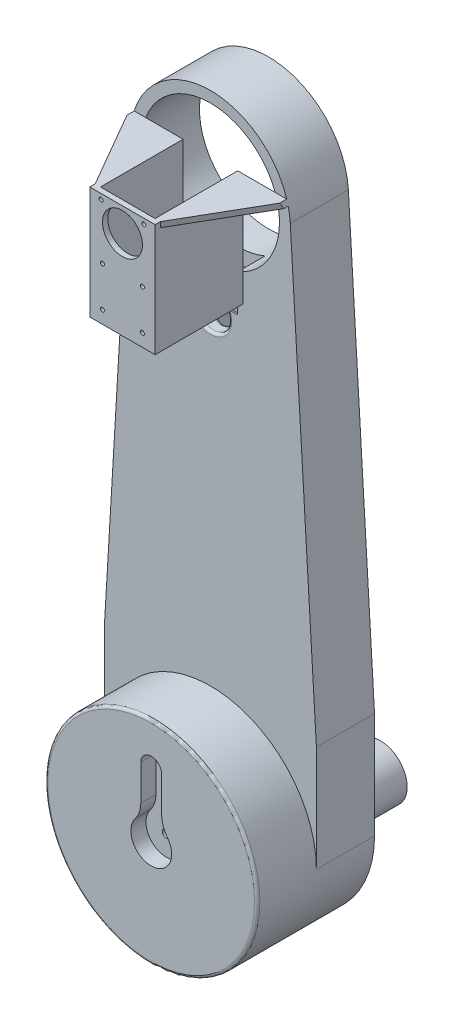
SolidWorks part; units mm, degrees
material "6061 Alloy"
ref_plane "Front Plane" through (0, 0, 0) normal (0, 0, 1) x (1, 0, 0)
ref_plane "Top Plane" through (0, 0, 0) normal (0, 1, 0) x (1, 0, 0)
ref_plane "Right Plane" through (0, 0, 0) normal (1, 0, 0) x (0, 0, -1)
sketch "Sketch1" plane through (0, 0, 0) normal (0, 0, 1) x (1, 0, 0)
  circle A0 centre (0, 0) radius 39.75
  dimension "D1" = 79.5
extrude "Boss-Extrude1" add sketch "Sketch1" along normal blind 44
sketch "Sketch2" plane through (0, 0, 0) normal (0, 1, 0) x (1, 0, 0)
  line L0 (39.75, -44) -> (39.75, 0) construction
  line L1 (-39.75, 0) -> (39.75, 0)
  line L2 (-39.75, 0) -> (-39.75, -21.8)
  line L3 (-39.75, -21.8) -> (39.75, -21.8)
  line L4 (39.75, 0) -> (39.75, -21.8)
  dimension "D1" = 21.8
extrude "Boss-Extrude2" add sketch "Sketch2" along normal through all
sketch "Sketch3" plane through (0, 0, 0) normal (0, 0, -1) x (-1, 0, 0)
  line L0 (0, 0) -> (0, 203.2) construction
  line L1 (-39.75, 39.75) -> (-29.9473, 204.9767)
  line L2 (39.75, 39.75) -> (29.9473, 204.9767)
  line L3 (39.75, 39.75) -> (39.75, 0) construction
  line L4 (-39.75, 39.75) -> (39.75, 39.75) construction
  circle A0 centre (0, 203.2) radius 30
  line M5 (39.75, 39.75) -> (-39.75, 39.75)
  dimension "D1" = 60
  dimension "D2" = 203.2
extrude "Boss-Extrude3" add sketch "Sketch3" against normal up to surface (21.8 mm away) contours L0 A0 L1 M5 | L0 L2 A0 M5 | A0 region at (18.2462, 107.3979, 0) region at (-18.2462, 107.3979, 0) region at (21.2148, 183.2065, 0) up to face at (29.2442, 29.2442, 21.8)
ref_plane "Plane7" through (0, 233.2, 0) normal (0, 1, 0) x (1, 0, 0)
sketch "Sketch5" plane through (0, 0, 21.8) normal (0, 0, 1) x (1, 0, 0)
  line L0 (10.25, 179.4146) -> (10.25, 171.95)
  line L1 (10.25, 171.95) -> (-10.25, 171.95)
  line L2 (-10.25, 171.95) -> (-10.25, 179.4146)
  circle A0 centre (0, 203.2) radius 25.9
  dimension "D1" = 20.5
  dimension "D4" = 51.8
  dimension "D6" = 7.4646
  dimension "D7" = 7.4646
extrude "Cut-Extrude2" cut sketch "Sketch5" against normal up to next contours A0 region at (0, 203.2, 21.8)
extrude "Cut-Extrude3" cut sketch "Sketch5<3>" against normal blind 10.25 contours A0 L2 L1 L0 region at (0, 175.0039, 21.8)
sketch "Sketch5<3>" plane through (0, 0, 21.8) normal (0, 0, 1) x (1, 0, 0) same geometry as "Sketch5"
sketch "Sketch7" plane through (0, 0, 21.8) normal (0, 0, 1) x (1, 0, 0)
  line L0 (-10.25, 171.95) -> (-10.25, 179.4146) construction
  line L1 (10.25, 171.95) -> (-12.25, 171.95)
  line L2 (10.25, 171.95) -> (10.25, 169.95)
  line L3 (10.25, 169.95) -> (-12.25, 169.95)
  line L4 (-12.25, 171.95) -> (-12.25, 169.95)
  line L6 (10.25, 169.95) -> (12.25, 169.95)
  line L7 (10.25, 169.95) -> (10.25, 212.2)
  line L8 (10.25, 212.2) -> (12.25, 212.2)
  line L9 (12.25, 169.95) -> (12.25, 212.2)
  line L10 (-12.25, 212.2) -> (-28.6182, 212.2)
  line L11 (-10.25, 171.95) -> (-12.25, 171.95)
  line L12 (-10.25, 171.95) -> (-10.25, 212.2)
  line L13 (-10.25, 212.2) -> (-12.25, 212.2)
  line L14 (-12.25, 171.95) -> (-12.25, 212.2)
  line L15 (-12.25, 210.2) -> (-29.1719, 210.2)
  line L16 (12.25, 212.2) -> (28.6182, 212.2)
  line L17 (12.25, 210.2) -> (29.1719, 210.2)
  line L18 (0, 203.2) -> (0, 212.2) construction
  line L19 (-10.25, 212.2) -> (10.25, 212.2) construction
  arc A0 (29.9473, 204.9767) -> (-29.9473, 204.9767) centre (0, 203.2) ccw construction
  arc A1 (-28.6182, 212.2) -> (-29.1719, 210.2) centre (0, 203.2) ccw
  arc A2 (29.1719, 210.2) -> (28.6182, 212.2) centre (0, 203.2) ccw
  arc M13 (29.9473, 204.9767) -> (-29.9473, 204.9767) centre (0, 203.2) ccw
  line M15 (10.25, 179.4146) -> (10.25, 171.95)
  line M16 (10.25, 171.95) -> (-10.25, 171.95)
  line M17 (-10.25, 171.95) -> (-10.25, 179.4146)
  arc M18 (-10.25, 179.4146) -> (10.25, 179.4146) centre (0, 203.2) cw
  dimension "D9" = 30
  dimension "D1" = 2
  dimension "D2" = 2
  dimension "D3" = 2
  dimension "D4" = 2
  dimension "D5" = 2
  dimension "D6" = 2
  dimension "D7" = 9
  dimension "D8" = 42.25
extrude "Boss-Extrude5" add sketch "Sketch7" along normal blind 31 contours L15 L14 L10 M18 | L15 L10 M18 M13 | L14 L12 L13 M18 | L14 L1 M17 M18 | L1 L4 L3 L2 M16 | L6 L9 L2 M18 M15 | L9 L8 L7 M18 | L9 L17 L16 M18 | L17 L16 M18 M13 region at (-1, 170.95, 21.8) region at (11.2662, 174.9188, 21.8) region at (-11.2703, 175.9197, 21.8) region at (11.245, 196.0386, 21.8) region at (-11.245, 196.0386, 21.8) region at (18.4394, 211.1912, 21.8) region at (26.7656, 211.2037, 21.8) region at (-18.4394, 211.1912, 21.8) region at (-26.7656, 211.2037, 21.8)
sketch "Sketch8" plane through (0, 212.2, 0) normal (0, 1, 0) x (1, 0, 0)
  line L0 (-29.1719, -23.4904) -> (-12.25, -52.8)
  line L1 (29.1719, -52.8) -> (29.1719, -21.8) construction
  line L2 (12.25, -52.8) -> (29.1719, -23.4904)
  line L4 (-29.1719, -52.8) -> (-29.1719, -21.8) construction
  line L6 (-29.1719, -23.4904) -> (-29.1719, -52.8)
  line L7 (-29.1719, -52.8) -> (-12.25, -52.8)
  line L8 (12.25, -52.8) -> (29.1719, -52.8)
  line L9 (29.1719, -52.8) -> (29.1719, -23.4904)
  line L11 (29.1719, -52.8) -> (29.1719, -21.8) construction
  dimension "D1" = 2
  dimension "D2" = 30
  dimension "D3" = 2
  dimension "D4" = 30
extrude "Cut-Extrude4" cut sketch "Sketch8" against normal blind 10
sketch "Sketch9" plane through (0, 0, 52.8) normal (0, 0, 1) x (1, 0, 0)
  line L0 (-12.25, 169.95) -> (-12.25, 180.3801) construction
  line L1 (-12.25, 169.95) -> (12.25, 169.95)
  line L2 (-12.25, 169.95) -> (-12.25, 212.2)
  line L3 (-12.25, 212.2) -> (12.25, 212.2)
  line L4 (12.25, 169.95) -> (12.25, 212.2)
  line L5 (-12.25, 169.95) -> (-12.25, 210.2) construction
  line L6 (-12.25, 169.95) -> (-7.5, 174.7) construction
  line L7 (-7.5, 174.7) -> (-7.5, 189.7) construction
  line L8 (-7.5, 189.7) -> (-8, 210.2) construction
  line L9 (-8, 210.2) -> (0, 203.2) construction
  line L10 (0, 203.2) -> (8, 210.2) construction
  line L11 (8, 210.2) -> (7.5, 189.7) construction
  line L12 (7.5, 189.7) -> (7.5, 174.7) construction
  line L13 (7.5, 174.7) -> (12.25, 169.95) construction
  circle A0 centre (0, 203.2) radius 7.5
  circle A1 centre (-8, 210.2) radius 0.75
  circle A2 centre (8, 210.2) radius 0.75
  circle A3 centre (7.5, 189.7) radius 0.75
  circle A4 centre (7.5, 174.7) radius 0.75
  circle A5 centre (-7.5, 174.7) radius 0.75
  circle A6 centre (-7.5, 189.7) radius 0.75
  line M25 (12.25, 210.2) -> (12.25, 212.2)
  line M26 (12.25, 212.2) -> (10.25, 212.2)
  line M27 (10.25, 212.2) -> (10.25, 171.95)
  line M28 (10.25, 171.95) -> (-10.25, 171.95)
  line M29 (-10.25, 171.95) -> (-10.25, 212.2)
  line M30 (-10.25, 212.2) -> (-12.25, 212.2)
  line M31 (-12.25, 212.2) -> (-12.25, 210.2)
  line M32 (-12.25, 210.2) -> (-12.25, 169.95)
  line M33 (-12.25, 169.95) -> (12.25, 169.95)
  line M34 (12.25, 169.95) -> (12.25, 210.2)
  dimension "D1" = 1.5
  dimension "D2" = 1.5
  dimension "D3" = 1.5
  dimension "D4" = 1.5
  dimension "D5" = 15
  dimension "D6" = 1.5
  dimension "D7" = 1.5
  dimension "D8" = 45
  dimension "D9" = 15
  dimension "D10" = 6.7175
  dimension "D11" = 20.5
  dimension "D12" = 10.6301
  dimension "D13" = 47.417
  dimension "D14" = 97.628
  dimension "D15" = 47.417
  dimension "D16" = 20.5
  dimension "D17" = 10.6301
  dimension "D18" = 15
extrude "Boss-Extrude6" add sketch "Sketch9" along normal blind 2 contours L3 A6 A5 A4 A3 A2 A1 A0 | M34 M25 M26 M27 M28 M29 M30 M31 M32 M33 region at (-11.7616, 190.075, 52.8) region at (0, 189.0016, 52.8)
sketch "Sketch10" plane through (0, 0, 0) normal (0, 0, -1) x (-1, 0, 0)
  line L0 (-20, 0) -> (20, 0) construction
  line L1 (0, 20) -> (0, -20) construction
  line L2 (0, 0) -> (0, 177.3) construction
  circle A1 centre (-20, 0) radius 10
  circle A2 centre (0, 20) radius 5
  circle A3 centre (20, 0) radius 10
  circle A4 centre (0, -20) radius 5
  circle A5 centre (0, 117.3) radius 5
  circle A6 centre (0, 147.3) radius 10
  circle A7 centre (0, 147.3) radius 5.125
  circle A8 centre (-20, 0) radius 5.125
  circle A9 centre (20, 0) radius 5.125
  circle A10 centre (0, 203.2) radius 25.9 construction
  point P5 (0, 0)
  point P9 (0, 0)
  dimension "D3" = 10
  dimension "D4" = 10
  dimension "D5" = 20
  dimension "D6" = 20
  dimension "D7" = 10
  dimension "D8" = 20
  dimension "D11" = 10.25
  dimension "D12" = 10.25
  dimension "D13" = 10.25
  dimension "D1" = 40
  dimension "D2" = 40
  dimension "D9" = 30
  dimension "D10" = 30
extrude "Boss-Extrude7" add sketch "Sketch10" along normal blind 22
sketch "Sketch11" plane through (0, 0, 0) normal (1, 0, 0) x (0, 0, -1)
  line L1 (-21.8, 161.95) -> (-18.9, 161.95)
  line L2 (-21.8, 204.9767) -> (-21.8, 39.75) construction
  line L3 (-10.9, 153.95) -> (-10.9, 161.95) construction
  line L4 (-10.9, 161.95) -> (-18.9, 161.95) construction
  line L8 (-54.8, 169.95) -> (-21.8, 169.95) construction
  line L18 (-10.9, -39.75) -> (-10.9, 153.95)
  line L22 (-44, -39.75) -> (0, -39.75) construction
  arc A0 (-18.9, 161.95) -> (-10.9, 153.95) centre (-18.9, 153.95) cw
  dimension "D4" = 8
  dimension "D1" = 10.9
  dimension "D2" = 8
  dimension "D3" = 2.9
sweep "Cut-Sweep1" cut path "Sketch11" circular profile diameter 12 parameters "D3"=12
fillet "Fillet3" radius 1 1 edges at (39.75, 0, 44)
sketch "Sketch14" plane through (0, 0, 0) normal (0, 0, -1) x (-1, 0, 0)
  line L0 (-5, -20) -> (5, -20)
  line L1 (-5, -20) -> (-27.8841, -28.3291)
  line L2 (5, -20) -> (27.8841, -28.3291)
  line L3 (-5, -20) -> (0, -18.1801)
  line L4 (0, -18.1801) -> (5, -20)
  circle A0 centre (0, -20) radius 5 construction
  circle A1 centre (0, -20) radius 5 construction
  arc A2 (-39.75, 0) -> (39.75, 0) centre (0, 0) ccw construction
  arc A3 (-27.8841, -28.3291) -> (27.8841, -28.3291) centre (0, 0) ccw
  circle M8 centre (0, -20) radius 5
  arc M18 (-39.75, 0) -> (39.75, 0) centre (0, 0) ccw
  dimension "D1" = 160
  dimension "D2" = 160
extrude "Cut-Extrude6(NEW)" cut sketch "Sketch14" against normal blind 21 and the other way blind 1 from offset 4.9 contours L2 L1 M8 M18 | L0 M8 | L4 L3 L0 region at (0, -19.3934, 0) region at (0, -30.4059, 0) region at (0, -22.1221, 0) offset against normal yes
fillet "Fillet4" radius 1 6 edges at (-13.942, -23.2546, 3.9) (-13.942, -23.2546, 25.9) (-27.8841, -28.3291, 14.9) (0, -39.75, 3.9) (27.8841, -28.3291, 14.9) (0, -39.75, 25.9)
sketch "Sketch20" plane through (0, 0, 21.8) normal (0, 0, 1) x (1, 0, 0)
  circle A1 centre (0, 161.95) radius 7
  dimension "D1" = 14
extrude "Cut-Extrude7(NEW)" cut sketch "Sketch20" against normal through all
sketch "Sketch22" plane through (0, 171.95, 0) normal (0, 1, 0) x (1, 0, 0)
  line L0 (0, -11.55) -> (0, -21.25) construction
  line L1 (10.25, -11.55) -> (-10.25, -11.55) construction
  line L2 (10.25, -11.55) -> (10.25, -52.8) construction
  line L3 (10.25, -21.25) -> (-10.25, -21.25)
  line L4 (10.25, -21.25) -> (10.25, -28.25)
  line L5 (10.25, -28.25) -> (-10.25, -28.25)
  line L6 (-10.25, -21.25) -> (-10.25, -28.25)
  line L7 (-10.25, -52.8) -> (-10.25, -21.8) construction
  dimension "D1" = 9.7
  dimension "D2" = 7
extrude "Cut-Extrude8" cut sketch "Sketch22" against normal blind 6.5
sketch "Sketch23" plane through (0, 0, 44) normal (0, 0, 1) x (1, 0, 0)
  line L1 (-3.725, 10.7762) -> (-3.725, 24.0717)
  line L7 (3, 24.0717) -> (3, 20.0717)
  line L12 (3.725, 10.7762) -> (3.725, 24.0717)
  line L13 (-3, 24.0717) -> (-3, 20.0717)
  line L14 (3.925, 10.7762) -> (3.925, 24.0717)
  line L15 (-3.925, 10.7762) -> (-3.925, 24.0717)
  arc A2 (3.725, 24.0717) -> (-3.725, 24.0717) centre (0, 24.0717) ccw
  arc A3 (3, 24.0717) -> (-3, 24.0717) centre (0, 24.0717) ccw
  arc A4 (-3.725, 6.4519) -> (-0.729, 7.4142) centre (0, 0) cw
  arc A5 (5.8597, 4.6007) -> (3.725, 10.7762) centre (13.725, 10.7762) cw
  arc A6 (-5.8597, 4.6007) -> (-3.725, 10.7762) centre (-13.725, 10.7762) ccw
  arc A7 (-6.017, 4.7242) -> (6.017, 4.7242) centre (0, 0) ccw
  arc A8 (6.017, 4.7242) -> (3.925, 10.7762) centre (13.725, 10.7762) cw
  arc A9 (3.925, 24.0717) -> (-3.925, 24.0717) centre (0, 24.0717) ccw
  arc A10 (-6.017, 4.7242) -> (-3.925, 10.7762) centre (-13.725, 10.7762) ccw
  circle A11 centre (0, 0) radius 1.5
  circle A12 centre (0, 8.95) radius 1.7
  circle A13 centre (0, 20.0717) radius 1.5
  circle A14 centre (0, 24.0717) radius 1.5
  arc A15 (0.729, 7.4142) -> (3.725, 6.4519) centre (0, 0) cw
  point P4 (0, 0)
  point P8 (0, 0)
  point P13 (0, 27.75)
  point P14 (0, 0)
  dimension "D4" = 6
  dimension "D1" = 7.45
  dimension "D5" = 10
  dimension "D6" = 3
  dimension "D7" = 3
  dimension "D8" = 3
  dimension "D2" = 24.0717
extrude "Cut-Extrude9(NEW)" cut sketch "Sketch23" against normal blind 5.67 contours A10 A7 A8 L14 A9 L15 A14 A13 A11 A12 region at (4.0961, 7.4478, 44)
sketch "Sketch24" plane through (-41.9606, 2.4895, 0) normal (-0.9982, 0.0592, 0) x (0, 0, 1)
  line L0 (2.0543, 49.6834) -> (2.0543, 53.2013)
  line L1 (15.2985, 60.554) -> (20.2543, 60.554)
  line L2 (20.2543, 60.554) -> (20.2543, 55.7564)
  line L3 (2.2543, 49.8834) -> (2.2543, 53.2013)
  line L4 (15.3, 60.354) -> (20.0543, 60.354)
  line L5 (20.0543, 60.354) -> (20.0543, 55.9564)
  line L6 (20.0543, 55.9564) -> (14.0337, 55.9564)
  line L7 (11.8872, 54.4905) -> (20.0543, 54.4905)
  line L8 (20.0543, 54.4905) -> (20.0543, 49.8834)
  line L9 (20.0543, 49.8834) -> (2.2543, 49.8834)
  line L10 (5.186, 54.4905) -> (9.1649, 54.4905)
  line L11 (7.5517, 55.9564) -> (6.5668, 55.9564)
  line L12 (2.2543, 71.8298) -> (2.2543, 79.7874)
  line L13 (2.2543, 79.7874) -> (5.8143, 79.7874)
  line L14 (5.8143, 79.7874) -> (5.8143, 76.4368)
  line L15 (5.8143, 76.4368) -> (9.1649, 76.4368)
  line L16 (9.1649, 76.4368) -> (9.1649, 79.578)
  line L17 (9.1649, 79.578) -> (12.5154, 79.578)
  line L18 (12.5154, 79.578) -> (12.5154, 76.4368)
  line L19 (12.5154, 76.4368) -> (16.4943, 76.4368)
  line L20 (16.4943, 76.4368) -> (16.4943, 79.9968)
  line L21 (16.4943, 79.9968) -> (20.0543, 79.9968)
  line L22 (20.0543, 79.9968) -> (20.0543, 71.8298)
  line L23 (20.0543, 71.8298) -> (2.2543, 71.8298)
  line L24 (2.2543, 91.0538) -> (2.2543, 94.5712)
  line L25 (8.5333, 101.9432) -> (14.7666, 101.9432)
  line L26 (20.0543, 96.9828) -> (20.0543, 91.0538)
  line L27 (20.0543, 91.0538) -> (2.2543, 91.0538)
  line L28 (5.186, 95.6608) -> (17.1225, 95.6608)
  line L29 (14.4885, 97.3361) -> (7.4372, 97.3361)
  line L30 (2.2543, 113.419) -> (2.2543, 118.1405)
  line L31 (14.1482, 124.3084) -> (15.8202, 124.3084)
  line L32 (20.0543, 118.8309) -> (20.0543, 113.419)
  line L33 (20.0543, 113.419) -> (2.2543, 113.419)
  line L34 (5.186, 118.026) -> (9.1649, 118.026)
  line L35 (11.8872, 118.026) -> (17.1225, 118.026)
  line L36 (15.3785, 119.7013) -> (13.6312, 119.7013)
  line L37 (2.2543, 140.3912) -> (20.0543, 140.3912)
  line L38 (20.0543, 140.3912) -> (20.0543, 135.7841)
  line L39 (20.0543, 135.7841) -> (2.2543, 135.7841)
  line L40 (2.2543, 135.7841) -> (2.2543, 140.3912)
  line L41 (2.2543, 152.0764) -> (2.2543, 155.3942)
  line L42 (15.3, 162.547) -> (20.0543, 162.547)
  line L43 (20.0543, 162.547) -> (20.0543, 158.1493)
  line L44 (20.0543, 158.1493) -> (14.0337, 158.1493)
  line L45 (11.8872, 156.6834) -> (20.0543, 156.6834)
  line L46 (20.0543, 156.6834) -> (20.0543, 152.0764)
  line L47 (20.0543, 152.0764) -> (2.2543, 152.0764)
  line L48 (5.186, 156.6834) -> (9.1649, 156.6834)
  line L49 (7.5517, 158.1493) -> (6.5668, 158.1493)
  line L50 (2.2543, 174.0227) -> (2.2543, 177.5402)
  line L51 (8.5333, 184.9121) -> (14.7666, 184.9121)
  line L52 (20.0543, 179.9517) -> (20.0543, 174.0227)
  line L53 (20.0543, 174.0227) -> (2.2543, 174.0227)
  line L54 (5.186, 178.6298) -> (17.1225, 178.6298)
  line L55 (14.4885, 180.3051) -> (7.4372, 180.3051)
  line L56 (20.2543, 55.7564) -> (14.0337, 55.7564)
  line L57 (12.0921, 54.6905) -> (20.2543, 54.6905)
  line L58 (20.2543, 54.6905) -> (20.2543, 49.6834)
  line L59 (20.2543, 49.6834) -> (2.0543, 49.6834)
  line L60 (5.3915, 54.6905) -> (8.9599, 54.6905)
  line L61 (7.5489, 55.7564) -> (6.5679, 55.7564)
  line L62 (2.0543, 71.6298) -> (2.0543, 79.9874)
  line L63 (2.0543, 79.9874) -> (6.0143, 79.9874)
  line L64 (6.0143, 79.9874) -> (6.0143, 76.6368)
  line L65 (6.0143, 76.6368) -> (8.9649, 76.6368)
  line L66 (8.9649, 76.6368) -> (8.9649, 79.778)
  line L67 (8.9649, 79.778) -> (12.7154, 79.778)
  line L68 (12.7154, 79.778) -> (12.7154, 76.6368)
  line L69 (12.7154, 76.6368) -> (16.2943, 76.6368)
  line L70 (16.2943, 76.6368) -> (16.2943, 80.1968)
  line L71 (16.2943, 80.1968) -> (20.2543, 80.1968)
  line L72 (20.2543, 80.1968) -> (20.2543, 71.6298)
  line L73 (20.2543, 71.6298) -> (2.0543, 71.6298)
  line L74 (8.5326, 102.1432) -> (14.7673, 102.1432)
  line L75 (20.2543, 96.9843) -> (20.2543, 90.8538)
  line L76 (20.2543, 90.8538) -> (2.0543, 90.8538)
  line L77 (2.0543, 90.8538) -> (2.0543, 94.5712)
  line L78 (5.3898, 95.8608) -> (16.9188, 95.8608)
  line L79 (14.4893, 97.1361) -> (7.4348, 97.1361)
  line L80 (14.1479, 124.5084) -> (15.8203, 124.5084)
  line L81 (20.2543, 118.8321) -> (20.2543, 113.219)
  line L82 (20.2543, 113.219) -> (2.0543, 113.219)
  line L83 (2.0543, 113.219) -> (2.0543, 118.1417)
  line L84 (5.3903, 118.226) -> (8.96, 118.226)
  line L85 (12.0964, 118.226) -> (16.9125, 118.226)
  line L86 (15.3808, 119.5013) -> (13.6314, 119.5013)
  line L87 (2.0543, 140.5912) -> (20.2543, 140.5912)
  line L88 (20.2543, 140.5912) -> (20.2543, 135.5841)
  line L89 (20.2543, 135.5841) -> (2.0543, 135.5841)
  line L90 (2.0543, 135.5841) -> (2.0543, 140.5912)
  line L95 (15.2985, 162.747) -> (20.2543, 162.747)
  line L96 (20.2543, 162.747) -> (20.2543, 157.9493)
  line L97 (20.2543, 157.9493) -> (14.0337, 157.9493)
  line L98 (12.0921, 156.8834) -> (20.2543, 156.8834)
  line L99 (20.2543, 156.8834) -> (20.2543, 151.8764)
  line L100 (20.2543, 151.8764) -> (2.0543, 151.8764)
  line L101 (2.0543, 151.8764) -> (2.0543, 155.3942)
  line L102 (5.3915, 156.8834) -> (8.9599, 156.8834)
  line L103 (7.5489, 157.9493) -> (6.5679, 157.9493)
  line L104 (8.5326, 185.1121) -> (14.7673, 185.1121)
  line L105 (20.2543, 179.9533) -> (20.2543, 173.8227)
  line L106 (20.2543, 173.8227) -> (2.0543, 173.8227)
  line L107 (2.0543, 173.8227) -> (2.0543, 177.5402)
  line L108 (5.3898, 178.8298) -> (16.9188, 178.8298)
  line L109 (14.4893, 180.1051) -> (7.4348, 180.1051)
  spline S0 degree 3 poles (2.2543, 53.2013) (2.2524, 53.7107) (2.2609, 54.4405) (2.2883, 55.3686) (2.3127, 55.9644) (2.3488, 56.4935) (2.3905, 56.955) (2.4378, 57.3495) (2.4964, 57.6866) (2.5727, 57.9837) (2.6729, 58.2579) (2.7922, 58.5203) (2.9412, 58.7678) (3.1161, 58.9986) (3.3084, 59.2211) (3.5318, 59.4236) (3.7758, 59.6184) (4.0541, 59.7945) (4.3701, 59.9435) (4.7229, 60.0713) (5.1139, 60.175) (5.5427, 60.2553) (6.1889, 60.3377) (6.6955, 60.3492) (7.0446, 60.354) knots 0 0 0 0 0.148881 0.213303 0.271377 0.323138 0.368276 0.406827 0.439217 0.468212 0.496346 0.524443 0.552325 0.580569 0.609028 0.638128 0.668547 0.700209 0.734143 0.770448 0.80973 0.852244 0.897872 1 1 1 1
  spline S1 degree 3 poles (7.0446, 60.354) (7.3581, 60.3592) (7.8079, 60.338) (8.3791, 60.289) (8.7445, 60.228) (9.0689, 60.1585) (9.3531, 60.0723) (9.5929, 59.964) (9.7974, 59.8411) (9.9702, 59.6911) (10.1214, 59.5118) (10.255, 59.3015) (10.3706, 59.0599) (10.4622, 58.7862) (10.5789, 58.3658) (10.6225, 58.0268) (10.6438, 57.792) knots 0 0 0 0 0.183844 0.264214 0.336185 0.401092 0.458783 0.510057 0.555172 0.598283 0.643683 0.692329 0.744143 0.800414 0.861431 1 1 1 1
  spline S2 degree 3 poles (10.6438, 57.792) (10.702, 58.0046) (10.7842, 58.3129) (10.9286, 58.6959) (11.0437, 58.9407) (11.1615, 59.1589) (11.2844, 59.3507) (11.4197, 59.5123) (11.6042, 59.6868) (11.8391, 59.8592) (12.1101, 60.033) (12.3707, 60.1602) (12.5927, 60.2331) (12.7952, 60.2659) (12.9969, 60.2928) (13.2526, 60.3098) (13.5602, 60.3264) (13.9202, 60.3387) (14.5058, 60.3539) (14.9717, 60.3492) (15.3, 60.354) knots 0 0 0 0 0.11021 0.159198 0.204304 0.245276 0.283065 0.317885 0.350264 0.409778 0.463156 0.510931 0.554366 0.579275 0.613344 0.655979 0.70728 0.767268 0.835956 1 1 1 1
  spline S3 degree 3 poles (14.0337, 55.9564) (13.8145, 55.9546) (13.503, 55.9546) (13.1117, 55.9259) (12.8692, 55.9007) (12.6605, 55.8685) (12.4855, 55.8318) (12.346, 55.7827) (12.2352, 55.7264) (12.1457, 55.6532) (12.0792, 55.5534) (12.0146, 55.4369) (11.9725, 55.2912) (11.9315, 55.1259) (11.8979, 54.8557) (11.8876, 54.6414) (11.8872, 54.4905) knots 0 0 0 0 0.208735 0.296167 0.373443 0.440695 0.497113 0.543415 0.581035 0.614932 0.652106 0.694368 0.741317 0.795712 0.856499 1 1 1 1
  spline S4 degree 3 poles (9.1649, 54.4905) (9.1598, 54.7207) (9.1563, 55.0454) (9.0543, 55.4227) (8.9778, 55.6032) (8.8784, 55.7115) (8.7778, 55.7812) (8.6441, 55.8339) (8.4829, 55.8793) (8.2922, 55.914) (7.9794, 55.9517) (7.7283, 55.9514) (7.5517, 55.9564) knots 0 0 0 0 0.26299 0.361623 0.442867 0.481356 0.526611 0.580322 0.643299 0.716254 0.799641 1 1 1 1
  spline S5 degree 3 poles (6.5668, 55.9564) (6.3319, 55.954) (6.0027, 55.9378) (5.6283, 55.7976) (5.4387, 55.6513) (5.3228, 55.4405) (5.199, 55.0583) (5.1906, 54.7253) (5.186, 54.4905) knots 0 0 0 0 0.296724 0.405999 0.497474 0.590179 0.702697 1 1 1 1
  spline S6 degree 3 poles (2.2543, 94.5712) (2.2491, 95.0927) (2.265, 95.841) (2.2922, 96.7934) (2.33, 97.4041) (2.3703, 97.9455) (2.4223, 98.4181) (2.4818, 98.8226) (2.5754, 99.2617) (2.7252, 99.7315) (2.9502, 100.2311) (3.2277, 100.6593) (3.5615, 101.0092) (3.9246, 101.2929) (4.3099, 101.5197) (4.7148, 101.6881) (5.0766, 101.7807) (5.3993, 101.8254) (5.6937, 101.8588) (6.0399, 101.8825) (6.4379, 101.9069) (6.8875, 101.921) (7.5919, 101.9412) (8.1462, 101.9404) (8.5333, 101.9432) knots 0 0 0 0 0.131285 0.188439 0.239882 0.285335 0.325123 0.359574 0.38823 0.438082 0.483425 0.52585 0.56587 0.6046 0.641526 0.678093 0.71466 0.735206 0.760074 0.789266 0.822551 0.860474 0.902505 1 1 1 1
  spline S7 degree 3 poles (14.7666, 101.9432) (15.133, 101.9409) (15.6581, 101.942) (16.3242, 101.9112) (16.75, 101.8915) (17.1252, 101.858) (17.452, 101.8209) (17.728, 101.7717) (18.0273, 101.7045) (18.3499, 101.5927) (18.69, 101.4099) (18.9916, 101.1908) (19.2402, 100.9191) (19.454, 100.6164) (19.6325, 100.2789) (19.7712, 99.9065) (19.8617, 99.5716) (19.9157, 99.2781) (19.9572, 99.0288) (19.9829, 98.752) (20.0113, 98.449) (20.0284, 98.1204) (20.0546, 97.6288) (20.0501, 97.2466) (20.0543, 96.9828) knots 0 0 0 0 0.124489 0.178253 0.226484 0.269248 0.306193 0.33817 0.36441 0.410339 0.453597 0.495164 0.536313 0.578044 0.620801 0.665593 0.712772 0.73842 0.766924 0.79859 0.832802 0.870285 0.910339 1 1 1 1
  spline S8 degree 3 poles (17.1225, 95.6608) (17.1216, 95.8332) (17.114, 96.0806) (17.0668, 96.3883) (17.0282, 96.5807) (16.9661, 96.7425) (16.9013, 96.8829) (16.8149, 96.9922) (16.7121, 97.0788) (16.5792, 97.1414) (16.4091, 97.1918) (16.1966, 97.2359) (15.9401, 97.2752) (15.6396, 97.3033) (15.1509, 97.3292) (14.7624, 97.3383) (14.4885, 97.3361) knots 0 0 0 0 0.13711 0.195797 0.247292 0.292516 0.333197 0.369593 0.402205 0.439011 0.485318 0.542921 0.611291 0.691374 0.782488 1 1 1 1
  spline S9 degree 3 poles (7.4372, 97.3361) (7.2506, 97.3407) (6.9845, 97.3318) (6.6475, 97.3241) (6.4358, 97.3151) (6.2517, 97.3001) (6.0949, 97.2908) (5.9668, 97.2688) (5.8339, 97.2467) (5.6966, 97.1938) (5.5516, 97.1104) (5.4354, 96.9895) (5.3332, 96.8397) (5.2685, 96.6339) (5.1899, 96.2406) (5.1913, 95.9043) (5.186, 95.6608) knots 0 0 0 0 0.161837 0.230941 0.292514 0.345641 0.39122 0.428559 0.458438 0.507835 0.555384 0.602223 0.652089 0.71135 0.787624 1 1 1 1
  spline S10 degree 3 poles (2.2543, 118.1405) (2.2583, 118.4906) (2.2613, 118.9994) (2.2964, 119.655) (2.3369, 120.0955) (2.3816, 120.5027) (2.4357, 120.8765) (2.5045, 121.216) (2.5827, 121.5259) (2.6782, 121.8122) (2.7961, 122.0801) (2.9347, 122.3336) (3.092, 122.5744) (3.2731, 122.8008) (3.4757, 123.0131) (3.7005, 123.2107) (3.9473, 123.3958) (4.2245, 123.5657) (4.5415, 123.7088) (4.8982, 123.8287) (5.2916, 123.9299) (5.7253, 124.0033) (6.3781, 124.0791) (6.8902, 124.1029) (7.2442, 124.099) knots 0 0 0 0 0.114375 0.166108 0.21439 0.258844 0.299904 0.337701 0.371916 0.404248 0.43615 0.467396 0.498519 0.529953 0.561953 0.594259 0.627603 0.66261 0.70023 0.740899 0.785396 0.832777 0.884431 1 1 1 1
  spline S11 degree 3 poles (7.2442, 124.099) (7.4812, 124.1027) (7.8229, 124.0851) (8.2564, 124.0306) (8.5398, 123.9816) (8.7925, 123.9072) (9.0192, 123.8256) (9.2154, 123.7222) (9.3876, 123.6029) (9.5377, 123.4558) (9.6806, 123.2859) (9.8049, 123.08) (9.9276, 122.8491) (10.0427, 122.5875) (10.1786, 122.1774) (10.2698, 121.8534) (10.3166, 121.6253) knots 0 0 0 0 0.159635 0.229972 0.294227 0.35305 0.407212 0.456169 0.502024 0.547743 0.597307 0.65111 0.709269 0.77341 0.843331 1 1 1 1
  spline S12 degree 3 poles (10.3166, 121.6253) (10.3725, 121.8692) (10.4727, 122.2201) (10.6533, 122.6535) (10.7959, 122.9376) (10.958, 123.1872) (11.1304, 123.4091) (11.3214, 123.5978) (11.5327, 123.7547) (11.7658, 123.8857) (12.0225, 124.0017) (12.3084, 124.0944) (12.6211, 124.173) (12.962, 124.2353) (13.4737, 124.2916) (13.873, 124.3075) (14.1482, 124.3084) knots 0 0 0 0 0.144043 0.209309 0.269932 0.32668 0.380292 0.431325 0.480651 0.531247 0.584899 0.64245 0.703941 0.770287 0.841669 1 1 1 1
  spline S13 degree 3 poles (15.8202, 124.3084) (16.105, 124.3082) (16.5181, 124.2978) (17.0491, 124.2528) (17.4031, 124.2086) (17.7275, 124.1492) (18.0218, 124.0783) (18.288, 123.994) (18.5975, 123.8656) (18.9388, 123.6678) (19.2809, 123.3602) (19.5501, 122.9886) (19.7172, 122.6267) (19.8132, 122.2867) (19.8782, 121.9685) (19.9313, 121.5913) (19.9769, 121.1537) (20.0114, 120.6582) (20.0492, 119.8774) (20.0492, 119.2617) (20.0543, 118.8309) knots 0 0 0 0 0.102269 0.148253 0.191288 0.230306 0.266588 0.299901 0.330446 0.386794 0.440584 0.494395 0.550463 0.582684 0.621084 0.666995 0.719365 0.779044 0.845298 1 1 1 1
  spline S14 degree 2 poles (9.1649, 118.026) (9.158, 118.2812) (9.155, 118.5365) knots 0 0 0 1 1 1
  spline S15 degree 3 poles (9.155, 118.5365) (9.1579, 118.7431) (9.133, 119.0337) (8.9824, 119.3569) (8.8469, 119.4881) (8.7043, 119.5504) (8.5607, 119.5934) (8.3767, 119.6219) (8.1545, 119.6526) (7.8934, 119.6739) (7.467, 119.6971) (7.1275, 119.7009) (6.8875, 119.7013) knots 0 0 0 0 0.207117 0.283923 0.350831 0.389245 0.438074 0.499907 0.574465 0.661754 0.760817 1 1 1 1
  spline S16 degree 3 poles (6.8875, 119.7013) (6.6489, 119.704) (6.3205, 119.6872) (5.9256, 119.6186) (5.7173, 119.5414) (5.558, 119.4472) (5.4338, 119.3409) (5.3385, 119.2221) (5.2761, 119.0788) (5.2385, 118.899) (5.197, 118.5455) (5.1898, 118.2464) (5.186, 118.026) knots 0 0 0 0 0.246774 0.340005 0.413619 0.475395 0.530632 0.582131 0.631661 0.690822 0.771636 1 1 1 1
  spline S17 degree 3 poles (17.1225, 118.026) (17.115, 118.1897) (17.1052, 118.4245) (17.063, 118.7183) (17.0287, 118.9036) (16.9825, 119.0642) (16.9314, 119.2017) (16.8737, 119.3159) (16.8016, 119.4067) (16.7101, 119.4781) (16.5984, 119.541) (16.4578, 119.5872) (16.2932, 119.6309) (16.1013, 119.6617) (15.7938, 119.6926) (15.55, 119.7054) (15.3785, 119.7013) knots 0 0 0 0 0.168584 0.241049 0.305039 0.362178 0.412572 0.455707 0.493181 0.530655 0.574326 0.624331 0.682257 0.749354 0.823771 1 1 1 1
  spline S18 degree 3 poles (13.6312, 119.7013) (13.4513, 119.7011) (13.1938, 119.6986) (12.873, 119.6632) (12.674, 119.6414) (12.5072, 119.6005) (12.3675, 119.5572) (12.2581, 119.5018) (12.172, 119.437) (12.1095, 119.3498) (12.059, 119.2406) (12.0133, 119.1045) (11.9755, 118.9411) (11.9432, 118.751) (11.9067, 118.4436) (11.8935, 118.1986) (11.8872, 118.026) knots 0 0 0 0 0.182344 0.260037 0.326886 0.384748 0.433642 0.474638 0.508444 0.541576 0.582078 0.629925 0.686713 0.751712 0.825136 1 1 1 1
  spline S19 degree 3 poles (2.2543, 155.3942) (2.2524, 155.9036) (2.2609, 156.6335) (2.2883, 157.5616) (2.3127, 158.1573) (2.3488, 158.6864) (2.3905, 159.148) (2.4378, 159.5424) (2.4964, 159.8795) (2.5727, 160.1766) (2.6729, 160.4508) (2.7922, 160.7132) (2.9412, 160.9607) (3.1161, 161.1916) (3.3084, 161.414) (3.5318, 161.6165) (3.7758, 161.8114) (4.0541, 161.9875) (4.3701, 162.1364) (4.7229, 162.2643) (5.1139, 162.368) (5.5427, 162.4483) (6.1889, 162.5306) (6.6955, 162.5421) (7.0446, 162.547) knots 0 0 0 0 0.148881 0.213303 0.271377 0.323138 0.368276 0.406827 0.439217 0.468212 0.496346 0.524443 0.552325 0.580569 0.609028 0.638128 0.668547 0.700209 0.734143 0.770448 0.80973 0.852244 0.897872 1 1 1 1
  spline S20 degree 3 poles (7.0446, 162.547) (7.3581, 162.5522) (7.8079, 162.5309) (8.3791, 162.4819) (8.7445, 162.421) (9.0689, 162.3514) (9.3531, 162.2653) (9.5929, 162.157) (9.7974, 162.034) (9.9702, 161.884) (10.1214, 161.7048) (10.255, 161.4944) (10.3706, 161.2528) (10.4622, 160.9792) (10.5789, 160.5588) (10.6225, 160.2197) (10.6438, 159.9849) knots 0 0 0 0 0.183844 0.264214 0.336185 0.401092 0.458783 0.510057 0.555172 0.598283 0.643683 0.692329 0.744143 0.800414 0.861431 1 1 1 1
  spline S21 degree 3 poles (10.6438, 159.9849) (10.702, 160.1975) (10.7842, 160.5059) (10.9286, 160.8889) (11.0437, 161.1337) (11.1615, 161.3519) (11.2844, 161.5436) (11.4197, 161.7052) (11.6042, 161.8797) (11.8391, 162.0522) (12.1101, 162.2259) (12.3707, 162.3531) (12.5927, 162.426) (12.7952, 162.4589) (12.9969, 162.4858) (13.2526, 162.5028) (13.5602, 162.5194) (13.9202, 162.5316) (14.5058, 162.5468) (14.9717, 162.5421) (15.3, 162.547) knots 0 0 0 0 0.11021 0.159198 0.204304 0.245276 0.283065 0.317885 0.350264 0.409778 0.463156 0.510931 0.554366 0.579275 0.613344 0.655979 0.70728 0.767268 0.835956 1 1 1 1
  spline S22 degree 3 poles (14.0337, 158.1493) (13.8145, 158.1475) (13.503, 158.1475) (13.1117, 158.1189) (12.8692, 158.0936) (12.6605, 158.0615) (12.4855, 158.0248) (12.346, 157.9756) (12.2352, 157.9194) (12.1457, 157.8461) (12.0792, 157.7464) (12.0146, 157.6299) (11.9725, 157.4842) (11.9315, 157.3189) (11.8979, 157.0486) (11.8876, 156.8343) (11.8872, 156.6834) knots 0 0 0 0 0.208735 0.296167 0.373443 0.440695 0.497113 0.543415 0.581035 0.614932 0.652106 0.694368 0.741317 0.795712 0.856499 1 1 1 1
  spline S23 degree 3 poles (9.1649, 156.6834) (9.1598, 156.9136) (9.1563, 157.2383) (9.0543, 157.6156) (8.9778, 157.7961) (8.8784, 157.9045) (8.7778, 157.9741) (8.6441, 158.0268) (8.4829, 158.0723) (8.2922, 158.1069) (7.9794, 158.1447) (7.7283, 158.1444) (7.5517, 158.1493) knots 0 0 0 0 0.26299 0.361623 0.442867 0.481356 0.526611 0.580322 0.643299 0.716254 0.799641 1 1 1 1
  spline S24 degree 3 poles (6.5668, 158.1493) (6.3319, 158.1469) (6.0027, 158.1307) (5.6283, 157.9905) (5.4387, 157.8442) (5.3228, 157.6334) (5.199, 157.2513) (5.1906, 156.9183) (5.186, 156.6834) knots 0 0 0 0 0.296724 0.405999 0.497474 0.590179 0.702697 1 1 1 1
  spline S25 degree 3 poles (2.2543, 177.5402) (2.2491, 178.0617) (2.265, 178.8099) (2.2922, 179.7623) (2.33, 180.373) (2.3703, 180.9145) (2.4223, 181.3871) (2.4818, 181.7915) (2.5754, 182.2306) (2.7252, 182.7005) (2.9502, 183.2001) (3.2277, 183.6283) (3.5615, 183.9782) (3.9246, 184.2619) (4.3099, 184.4886) (4.7148, 184.657) (5.0766, 184.7496) (5.3993, 184.7943) (5.6937, 184.8277) (6.0399, 184.8515) (6.4379, 184.8758) (6.8875, 184.8899) (7.5919, 184.9102) (8.1462, 184.9093) (8.5333, 184.9121) knots 0 0 0 0 0.131285 0.188439 0.239882 0.285335 0.325123 0.359574 0.38823 0.438082 0.483425 0.52585 0.56587 0.6046 0.641526 0.678093 0.71466 0.735206 0.760074 0.789266 0.822551 0.860474 0.902505 1 1 1 1
  spline S26 degree 3 poles (14.7666, 184.9121) (15.133, 184.9098) (15.6581, 184.911) (16.3242, 184.8802) (16.75, 184.8605) (17.1252, 184.8269) (17.452, 184.7898) (17.728, 184.7407) (18.0273, 184.6735) (18.3499, 184.5617) (18.69, 184.3789) (18.9916, 184.1597) (19.2402, 183.8881) (19.454, 183.5854) (19.6325, 183.2478) (19.7712, 182.8754) (19.8617, 182.5405) (19.9157, 182.2471) (19.9572, 181.9977) (19.9829, 181.7209) (20.0113, 181.418) (20.0284, 181.0893) (20.0546, 180.5978) (20.0501, 180.2155) (20.0543, 179.9517) knots 0 0 0 0 0.124489 0.178253 0.226484 0.269248 0.306193 0.33817 0.36441 0.410339 0.453597 0.495164 0.536313 0.578044 0.620801 0.665593 0.712772 0.73842 0.766924 0.79859 0.832802 0.870285 0.910339 1 1 1 1
  spline S27 degree 3 poles (17.1225, 178.6298) (17.1216, 178.8021) (17.114, 179.0495) (17.0668, 179.3572) (17.0282, 179.5497) (16.9661, 179.7115) (16.9013, 179.8519) (16.8149, 179.9612) (16.7121, 180.0477) (16.5792, 180.1103) (16.4091, 180.1607) (16.1966, 180.2048) (15.9401, 180.2442) (15.6396, 180.2723) (15.1509, 180.2981) (14.7624, 180.3073) (14.4885, 180.3051) knots 0 0 0 0 0.13711 0.195797 0.247292 0.292516 0.333197 0.369593 0.402205 0.439011 0.485318 0.542921 0.611291 0.691374 0.782488 1 1 1 1
  spline S28 degree 3 poles (7.4372, 180.3051) (7.2506, 180.3096) (6.9845, 180.3007) (6.6475, 180.293) (6.4358, 180.2841) (6.2517, 180.2691) (6.0949, 180.2597) (5.9668, 180.2377) (5.8339, 180.2156) (5.6966, 180.1627) (5.5516, 180.0794) (5.4354, 179.9585) (5.3332, 179.8086) (5.2685, 179.6029) (5.1899, 179.2096) (5.1913, 178.8733) (5.186, 178.6298) knots 0 0 0 0 0.161837 0.230941 0.292514 0.345641 0.39122 0.428559 0.458438 0.507835 0.555384 0.602223 0.652089 0.71135 0.787624 1 1 1 1
  spline S29 degree 1 poles (2.0543, 53.2013) (7.0415, 60.554) knots 0 0 1 1 construction
  spline S30 degree 1 poles (7.0415, 60.554) (10.7031, 58.6618) knots 0 0 1 1 construction
  spline S31 degree 1 poles (10.7031, 58.6618) (15.2985, 60.554) knots 0 0 1 1 construction
  spline S32 degree 1 poles (14.0337, 55.7564) (12.0921, 54.6905) knots 0 0 1 1 construction
  spline S33 degree 3 poles (2.0543, 53.2013) (2.0512, 54.0598) (2.0724, 55.3508) (2.1791, 57.0578) (2.4067, 58.4016) (3.2334, 59.5508) (4.4263, 60.2569) (5.7419, 60.5158) (6.6066, 60.548) (7.0415, 60.554) knots 0.00007 0.00007 0.00007 0.00007 0.250046 0.375034 0.500022 0.62501 0.749998 0.874985 0.999973 0.999973 0.999973 0.999973
  spline S34 degree 3 poles (7.0415, 60.554) (7.4049, 60.56) (8.1306, 60.5271) (9.0394, 60.4018) (9.7715, 60.1289) (10.2519, 59.7203) (10.5443, 59.2007) (10.6548, 58.8441) (10.7031, 58.6618) knots 0.000053 0.000053 0.000053 0.000053 0.209433 0.418812 0.523502 0.628192 0.732882 0.837572 0.837572 0.837572 0.837572
  spline S35 degree 3 poles (10.7031, 58.6618) (10.7848, 58.8729) (10.9659, 59.2789) (11.4411, 59.8503) (11.911, 60.1538) (12.3286, 60.3661) (12.8128, 60.4905) (13.3509, 60.5154) (14.2222, 60.5544) (14.8668, 60.5477) (15.2985, 60.554) knots 0.139052 0.139052 0.139052 0.139052 0.246701 0.35435 0.461999 0.515824 0.569649 0.677298 0.784947 1.000245 1.000245 1.000245 1.000245
  spline S36 degree 3 poles (14.0337, 55.7564) (13.7923, 55.7544) (13.4274, 55.7535) (12.953, 55.7101) (12.6034, 55.6628) (12.3495, 55.5749) (12.2704, 55.4858) (12.1227, 55.22) (12.1024, 54.9129) (12.0921, 54.6905) knots 0.000524 0.000524 0.000524 0.000524 0.233788 0.35042 0.467053 0.583685 0.642001 0.700317 0.933582 0.933582 0.933582 0.933582
  spline S37 degree 1 poles (6.5679, 55.7564) (5.3915, 54.6905) knots 0 0 1 1 construction
  spline S38 degree 1 poles (8.9599, 54.6905) (7.5489, 55.7564) knots 0 0 1 1 construction
  spline S39 degree 3 poles (6.5679, 55.7564) (6.3975, 55.7546) (6.0456, 55.7394) (5.6688, 55.6115) (5.5329, 55.4211) (5.4201, 55.1136) (5.3981, 54.8574) (5.3915, 54.6905) knots 0.000432 0.000432 0.000432 0.000432 0.228515 0.456599 0.57064 0.684682 0.912765 0.912765 0.912765 0.912765
  spline S40 degree 3 poles (8.9599, 54.6905) (8.9538, 54.8781) (8.9301, 55.1667) (8.8086, 55.5118) (8.6928, 55.6102) (8.4223, 55.6918) (8.0514, 55.7487) (7.7465, 55.7509) (7.5489, 55.7564) knots 0.07818 0.07818 0.07818 0.07818 0.308374 0.423471 0.538568 0.653665 0.768762 0.998955 0.998955 0.998955 0.998955
  spline S41 degree 1 poles (2.0543, 94.5712) (8.5326, 102.1432) knots 0 0 1 1 construction
  spline S42 degree 1 poles (14.7673, 102.1432) (20.2543, 96.9843) knots 0 0 1 1 construction
  spline S43 degree 3 poles (2.0543, 94.5712) (2.0493, 95.07) (2.0653, 96.0678) (2.1297, 97.562) (2.2671, 99.0681) (2.7867, 100.5786) (3.7831, 101.5118) (4.7628, 101.9385) (5.8003, 102.0891) (7.0375, 102.132) (8.0348, 102.1396) (8.5326, 102.1432) knots 0.000165 0.000165 0.000165 0.000165 0.125152 0.250139 0.375126 0.500113 0.6251 0.687594 0.750087 0.875074 1.000061 1.000061 1.000061 1.000061
  spline S44 degree 3 poles (14.7673, 102.1432) (15.137, 102.1408) (15.8766, 102.1389) (16.9856, 102.0817) (18.1245, 101.9562) (19.227, 101.3717) (19.8849, 100.3427) (20.2515, 98.8386) (20.2425, 97.7296) (20.2543, 96.9843) knots -0.000072 -0.000072 -0.000072 -0.000072 0.124959 0.249991 0.375022 0.500053 0.625084 0.750116 1.000178 1.000178 1.000178 1.000178
  spline S45 degree 1 poles (7.4348, 97.1361) (5.3898, 95.8608) knots 0 0 1 1 construction
  spline S46 degree 1 poles (16.9188, 95.8608) (14.4893, 97.1361) knots 0 0 1 1 construction
  spline S47 degree 3 poles (7.4348, 97.1361) (7.1675, 97.1427) (6.769, 97.1319) (6.2273, 97.1009) (5.733, 97.0549) (5.4189, 96.6894) (5.3951, 96.1151) (5.3898, 95.8608) knots -0.000705 -0.000705 -0.000705 -0.000705 0.234687 0.352383 0.47008 0.705472 0.940865 0.940865 0.940865 0.940865
  spline S48 degree 3 poles (16.9188, 95.8608) (16.9092, 96.1326) (16.8446, 96.6066) (16.629, 96.939) (16.233, 97.0287) (15.8068, 97.0926) (15.226, 97.1269) (14.7831, 97.1385) (14.4893, 97.1361) knots 0.054835 0.054835 0.054835 0.054835 0.29118 0.409352 0.527524 0.645697 0.763869 1.000214 1.000214 1.000214 1.000214
  spline S49 degree 1 poles (2.0543, 118.1417) (7.2437, 124.299) knots 0 0 1 1 construction
  spline S50 degree 1 poles (7.2437, 124.299) (10.3246, 122.3682) knots 0 0 1 1 construction
  spline S51 degree 1 poles (10.3246, 122.3682) (14.1479, 124.5084) knots 0 0 1 1 construction
  spline S52 degree 1 poles (15.8203, 124.5084) (20.2543, 118.8321) knots 0 0 1 1 construction
  spline S53 degree 3 poles (2.0543, 118.1417) (2.0632, 118.9137) (2.0974, 120.0626) (2.3457, 121.6217) (2.8822, 122.7419) (3.7686, 123.6004) (4.9075, 124.0884) (6.0747, 124.262) (6.8537, 124.3032) (7.2437, 124.299) knots -0.000126 -0.000126 -0.000126 -0.000126 0.249834 0.374814 0.499795 0.624775 0.749755 0.874735 0.999715 0.999715 0.999715 0.999715
  spline S54 degree 3 poles (7.2437, 124.299) (7.5656, 124.3039) (8.2038, 124.2586) (9.02, 124.0953) (9.6262, 123.6903) (10.0456, 123.1267) (10.2259, 122.6801) (10.3246, 122.3682) knots 0.000583 0.000583 0.000583 0.000583 0.210772 0.42096 0.526055 0.631149 0.841338 0.841338 0.841338 0.841338
  spline S55 degree 3 poles (10.3246, 122.3682) (10.4595, 122.7398) (10.7127, 123.2738) (11.3078, 123.8742) (12.0318, 124.2568) (12.9993, 124.4722) (13.7635, 124.5072) (14.1479, 124.5084) knots 0.134807 0.134807 0.134807 0.134807 0.35112 0.459277 0.567433 0.783746 1.00006 1.00006 1.00006 1.00006
  spline S56 degree 3 poles (15.8203, 124.5084) (16.174, 124.5081) (16.8802, 124.4849) (17.9423, 124.3435) (19.0078, 123.9538) (19.8196, 123.0815) (20.1061, 121.9796) (20.1994, 120.9339) (20.2499, 119.8764) (20.2502, 119.181) (20.2543, 118.8321) knots -0.000009 -0.000009 -0.000009 -0.000009 0.125009 0.250028 0.375047 0.500065 0.625084 0.750102 0.875121 1.00014 1.00014 1.00014 1.00014
  spline S57 degree 1 poles (6.8862, 119.5013) (5.3903, 118.226) knots 0 0 1 1 construction
  spline S58 degree 1 poles (8.96, 118.226) (8.955, 118.5367) knots 0 0 1 1 construction
  spline S59 degree 1 poles (8.955, 118.5367) (6.8862, 119.5013) knots 0 0 1 1 construction
  spline S60 degree 3 poles (6.8862, 119.5013) (6.6712, 119.5037) (6.228, 119.4872) (5.745, 119.3613) (5.4948, 119.1284) (5.415, 118.8012) (5.3962, 118.4413) (5.3903, 118.226) knots -0.000333 -0.000333 -0.000333 -0.000333 0.232017 0.464368 0.580543 0.696718 0.929068 0.929068 0.929068 0.929068
  spline S61 degree 2 poles (8.96, 118.226) (8.9568, 118.3813) (8.955, 118.5367) knots 0.399977 0.399977 0.399977 1.004997 1.004997 1.004997
  spline S62 degree 3 poles (8.955, 118.5367) (8.958, 118.7535) (8.8995, 119.1532) (8.7077, 119.359) (8.3642, 119.4257) (8, 119.4677) (7.5087, 119.4958) (7.1345, 119.5009) (6.8862, 119.5013) knots -0.000852 -0.000852 -0.000852 -0.000852 0.249441 0.374588 0.499734 0.624881 0.750027 1.000321 1.000321 1.000321 1.000321
  spline S63 degree 1 poles (13.6314, 119.5013) (12.0964, 118.226) knots 0 0 1 1 construction
  spline S64 degree 1 poles (16.9125, 118.226) (15.3808, 119.5013) knots 0 0 1 1 construction
  spline S65 degree 3 poles (13.6314, 119.5013) (13.4092, 119.501) (13.0683, 119.4855) (12.6461, 119.44) (12.3902, 119.3519) (12.3052, 119.2901) (12.2304, 119.1439) (12.1373, 118.7817) (12.1086, 118.4458) (12.0964, 118.226) knots 0.000048 0.000048 0.000048 0.000048 0.232207 0.348287 0.464367 0.522407 0.580447 0.696527 0.928687 0.928687 0.928687 0.928687
  spline S66 degree 3 poles (16.9125, 118.226) (16.9005, 118.4394) (16.8698, 118.7619) (16.7404, 119.169) (16.57, 119.3753) (16.0284, 119.4826) (15.5971, 119.5064) (15.3808, 119.5013) knots 0.072463 0.072463 0.072463 0.072463 0.304549 0.420592 0.536635 0.76872 1.000806 1.000806 1.000806 1.000806
  spline S67 degree 1 poles (2.0543, 155.3942) (7.0415, 162.7469) knots 0 0 1 1 construction
  spline S68 degree 1 poles (7.0415, 162.7469) (10.7031, 160.8547) knots 0 0 1 1 construction
  spline S69 degree 1 poles (10.7031, 160.8547) (15.2985, 162.747) knots 0 0 1 1 construction
  spline S70 degree 1 poles (14.0337, 157.9493) (12.0921, 156.8834) knots 0 0 1 1 construction
  spline S71 degree 3 poles (2.0543, 155.3942) (2.0512, 156.2528) (2.0724, 157.5437) (2.1791, 159.2507) (2.4067, 160.5945) (3.2334, 161.7437) (4.4263, 162.4499) (5.7419, 162.7087) (6.6066, 162.7409) (7.0415, 162.7469) knots 0.00007 0.00007 0.00007 0.00007 0.250046 0.375034 0.500022 0.62501 0.749998 0.874985 0.999973 0.999973 0.999973 0.999973
  spline S72 degree 3 poles (7.0415, 162.7469) (7.4049, 162.7529) (8.1306, 162.7201) (9.0394, 162.5948) (9.7715, 162.3219) (10.2519, 161.9133) (10.5443, 161.3936) (10.6548, 161.037) (10.7031, 160.8547) knots 0.000053 0.000053 0.000053 0.000053 0.209433 0.418812 0.523502 0.628192 0.732882 0.837572 0.837572 0.837572 0.837572
  spline S73 degree 3 poles (10.7031, 160.8547) (10.7848, 161.0658) (10.9659, 161.4718) (11.4411, 162.0433) (11.911, 162.3468) (12.3286, 162.5591) (12.8128, 162.6835) (13.3509, 162.7083) (14.2222, 162.7473) (14.8668, 162.7406) (15.2985, 162.747) knots 0.139052 0.139052 0.139052 0.139052 0.246701 0.35435 0.461999 0.515824 0.569649 0.677298 0.784947 1.000245 1.000245 1.000245 1.000245
  spline S74 degree 3 poles (14.0337, 157.9493) (13.7923, 157.9473) (13.4274, 157.9464) (12.953, 157.9031) (12.6034, 157.8557) (12.3495, 157.7678) (12.2704, 157.6788) (12.1227, 157.4129) (12.1024, 157.1058) (12.0921, 156.8834) knots 0.000524 0.000524 0.000524 0.000524 0.233788 0.35042 0.467053 0.583685 0.642001 0.700317 0.933582 0.933582 0.933582 0.933582
  spline S75 degree 1 poles (6.5679, 157.9493) (5.3915, 156.8834) knots 0 0 1 1 construction
  spline S76 degree 1 poles (8.9599, 156.8834) (7.5489, 157.9493) knots 0 0 1 1 construction
  spline S77 degree 3 poles (6.5679, 157.9493) (6.3975, 157.9476) (6.0456, 157.9324) (5.6688, 157.8045) (5.5329, 157.614) (5.4201, 157.3065) (5.3981, 157.0504) (5.3915, 156.8834) knots 0.000432 0.000432 0.000432 0.000432 0.228515 0.456599 0.57064 0.684682 0.912765 0.912765 0.912765 0.912765
  spline S78 degree 3 poles (8.9599, 156.8834) (8.9538, 157.0711) (8.9301, 157.3596) (8.8086, 157.7047) (8.6928, 157.8031) (8.4223, 157.8848) (8.0514, 157.9417) (7.7465, 157.9438) (7.5489, 157.9493) knots 0.07818 0.07818 0.07818 0.07818 0.308374 0.423471 0.538568 0.653665 0.768762 0.998955 0.998955 0.998955 0.998955
  spline S79 degree 1 poles (2.0543, 177.5402) (8.5326, 185.1121) knots 0 0 1 1 construction
  spline S80 degree 1 poles (14.7673, 185.1121) (20.2543, 179.9533) knots 0 0 1 1 construction
  spline S81 degree 3 poles (2.0543, 177.5402) (2.0493, 178.0389) (2.0653, 179.0368) (2.1297, 180.531) (2.2671, 182.0371) (2.7867, 183.5476) (3.7831, 184.4807) (4.7628, 184.9074) (5.8003, 185.0581) (7.0375, 185.1009) (8.0348, 185.1085) (8.5326, 185.1121) knots 0.000165 0.000165 0.000165 0.000165 0.125152 0.250139 0.375126 0.500113 0.6251 0.687594 0.750087 0.875074 1.000061 1.000061 1.000061 1.000061
  spline S82 degree 3 poles (14.7673, 185.1121) (15.137, 185.1098) (15.8766, 185.1079) (16.9856, 185.0506) (18.1245, 184.9251) (19.227, 184.3406) (19.8849, 183.3116) (20.2515, 181.8076) (20.2425, 180.6985) (20.2543, 179.9533) knots -0.000072 -0.000072 -0.000072 -0.000072 0.124959 0.249991 0.375022 0.500053 0.625084 0.750116 1.000178 1.000178 1.000178 1.000178
  spline S83 degree 1 poles (7.4348, 180.1051) (5.3898, 178.8298) knots 0 0 1 1 construction
  spline S84 degree 1 poles (16.9188, 178.8298) (14.4893, 180.1051) knots 0 0 1 1 construction
  spline S85 degree 3 poles (7.4348, 180.1051) (7.1675, 180.1116) (6.769, 180.1008) (6.2273, 180.0698) (5.733, 180.0239) (5.4189, 179.6584) (5.3951, 179.084) (5.3898, 178.8298) knots -0.000705 -0.000705 -0.000705 -0.000705 0.234687 0.352383 0.47008 0.705472 0.940865 0.940865 0.940865 0.940865
  spline S86 degree 3 poles (16.9188, 178.8298) (16.9092, 179.1016) (16.8446, 179.5756) (16.629, 179.9079) (16.233, 179.9976) (15.8068, 180.0616) (15.226, 180.0959) (14.7831, 180.1074) (14.4893, 180.1051) knots 0.054835 0.054835 0.054835 0.054835 0.29118 0.409352 0.527524 0.645697 0.763869 1.000214 1.000214 1.000214 1.000214
  dimension "D1" = 0.2
  dimension "D2" = 0.2
  dimension "D3" = 0.2
  dimension "D4" = 0.2
  dimension "D5" = 0.2
  dimension "D6" = 0.2
  dimension "D7" = 0.2
  dimension "D8" = 0.2
  dimension "D9" = 0.2
  dimension "D10" = 0.2
  dimension "D11" = 0.2
  dimension "D12" = 0.2
extrude "Cut-Extrude10" cut sketch "Sketch24" against normal blind 2 contours S36 L56 L2 L1 S35 S34 S33 L0 L59 L58 L57 L6 S3 L7 L8 L9 L3 S0 S1 S2 L4 L5 | S3 L6 L5 L4 S2 S1 S0 L3 L9 L8 L7 S5 L11 S4 L10 | L11 S5 L10 S4 S40 L60 S39 L61 | L73 L72 L71 L70 L69 L68 L67 L66 L65 L64 L63 L62 L22 L23 L12 L13 L14 L15 L16 L17 L18 L19 L20 L21 | L23 L22 L21 L20 L19 L18 L17 L16 L15 L14 L13 L12 | L29 S9 L28 S8 S48 L78 S47 L79 | S7 L25 S6 L24 L27 L26 S9 L29 S8 L28 | S44 L74 S43 L77 L76 L75 L25 S7 L26 L27 L24 S6 | S15 S16 L34 S14 S62 S61 L84 S60 | S13 L31 S12 S11 S10 L30 L33 L32 S18 L36 S17 L35 S16 S15 S14 L34 | L36 S18 L35 S17 S66 L85 S65 L86 | S56 L80 S55 S54 S53 L83 L82 L81 L31 S13 L32 L33 L30 S10 S11 S12 | L90 L89 L88 L87 L39 L40 L37 L38 | L40 L39 L38 L37 | L49 S24 L48 S23 S78 L102 S77 L103 | S22 L44 L43 L42 S21 S20 S19 L41 L47 L46 L45 S24 L49 S23 L48 | S74 L97 L96 L95 S73 S72 S71 L101 L100 L99 L98 L44 S22 L45 L46 L47 L41 S19 S20 S21 L42 L43 | S26 L51 S25 L50 L53 L52 S28 L55 S27 L54 | L55 S28 L54 S27 S86 L108 S85 L109 | S82 L104 S81 L107 L106 L105 L51 S26 L52 L53 L50 S25 region at (-38.914, 53.8415, 2.0755) region at (-38.7072, 57.3267, 11.1093) region at (-38.6671, 58.0025, 5.4798) region at (-37.4993, 77.6857, 11.1714) region at (-36.4638, 95.1391, 2.4629) region at (-36.2105, 99.409, 5.7697) region at (-34.9388, 120.8445, 11.2653) region at (-34.8914, 121.6426, 5.5274) region at (-34.8887, 121.6891, 12.2298) region at (-33.7825, 140.3347, 11.1543) region at (-32.6549, 159.3402, 11.1093) region at (-32.6148, 160.016, 5.4798) region at (-31.5501, 177.9624, 2.4629) region at (-31.2967, 182.2323, 5.7697) region at (-37.4709, 78.165, 2.0744) region at (-35.9125, 104.432, 11.6499) region at (-34.5879, 126.7579, 14.9841) region at (-33.6454, 142.6454, 11.1543) region at (-32.3233, 164.9296, 17.7764) region at (-30.9987, 187.2553, 11.6499)
sketch "Sketch25" plane through (0, 171.95, 0) normal (0, 1, 0) x (1, 0, 0)
  line L0 (10.25, -21.25) -> (-10.25, -21.25) construction
  line L1 (-1.25, -21.25) -> (1.25, -21.25)
  line L2 (-1.25, -21.25) -> (-1.25, -17.75)
  line L3 (-1.25, -17.75) -> (1.25, -17.75)
  line L4 (1.25, -21.25) -> (1.25, -17.75)
  line L5 (0, -21.25) -> (0, 0) construction
  dimension "D1" = 2.5
  dimension "D2" = 3.5
extrude "Cut-Extrude12" cut sketch "Sketch25" against normal blind 10
fillet "Fillet5" radius 1 13 edges at (-4.2207, 156.3656, -11) (0, 154.95, -22) (4.2207, 156.3656, -11) (0, 168.95, 0) (1.25, 168.8375, 19.5) (4.0294, 167.674, 21.25) (6.0622, 165.45, 21.525) (0, 154.95, 21.8) (-6.0622, 165.45, 21.525) (-4.0294, 167.674, 21.25) (-1.25, 168.8375, 19.5) (0, 168.95, 17.75) (5.4524, 157.5601, 14.7563)
extrude "Cut-Extrude13 (NEW)" cut sketch "Sketch23<3>" along direction (0, 0, 1) on the side against the normal blind 18 contours A11 | A12 | A13 | A14 region at (0, 0, 44) region at (0, 8.95, 44) region at (0, 20.0717, 44) region at (0, 24.0717, 44)
sketch "Sketch23<3>" plane through (0, 0, 44) normal (0, 0, 1) x (1, 0, 0) same geometry as "Sketch23"
thread "Thread2(NEW)" pitch 0.5 method extrude profile "Thread Profile2" start angle 0, offset 0, length 0, pitch 0.5, diameter 3
ref_plane "Plane9" through (-1.5, 20.0717, 38.33) normal (0, -1, 0) x (-1, 0, 0)
sketch "Thread Profile2" plane through (-1.5, 20.0717, 38.33) normal (0, -1, 0) x (-1, 0, 0)
  line L0 (0, 0) -> (0, 0.5) construction
  line L11 (0, 0) -> (0, 0.4375)
  line L12 (0, 0.4375) -> (-0.2706, 0.2812)
  line L13 (-0.2706, 0.2812) -> (-0.2706, 0.1562)
  line L15 (-0.2706, 0.1562) -> (0, 0)
  line L17 (-0.2706, 0.2187) -> (0, 0.2187) construction
  point P2 (0, 0)
  dimension "Pitch" = 0.5
  dimension "Profile_Angle" = 60
  dimension "Profile_Land" = 0.125
  dimension "Profile_Height" = 0.2706
thread "Thread3(NEW)" pitch 0.5 method extrude profile "Thread Profile3" start angle 0, offset 0, length 0, pitch 0.5, diameter 3
ref_plane "Plane10" through (-1.5, 24.0717, 38.33) normal (0, -1, 0) x (-1, 0, 0)
sketch "Thread Profile3" plane through (-1.5, 24.0717, 38.33) normal (0, -1, 0) x (-1, 0, 0)
  line L0 (0, 0) -> (0, 0.5) construction
  line L11 (0, 0) -> (0, 0.4375)
  line L12 (0, 0.4375) -> (-0.2706, 0.2812)
  line L13 (-0.2706, 0.2812) -> (-0.2706, 0.1562)
  line L15 (-0.2706, 0.1562) -> (0, 0)
  line L17 (-0.2706, 0.2187) -> (0, 0.2187) construction
  point P2 (0, 0)
  dimension "Pitch" = 0.5
  dimension "Profile_Angle" = 60
  dimension "Profile_Land" = 0.125
  dimension "Profile_Height" = 0.2706
thread "Thread1(NEW)" pitch 0.5 method extrude profile "Thread Profile4" start angle 0, offset 0, length 0, pitch 0.5, diameter 3.4
ref_plane "Plane11" through (-1.7, 8.95, 38.33) normal (0, -1, 0) x (-1, 0, 0)
sketch "Thread Profile4" plane through (-1.7, 8.95, 38.33) normal (0, -1, 0) x (-1, 0, 0)
  line L0 (0, 0) -> (0, 0.5) construction
  line L11 (0, 0) -> (0, 0.4375)
  line L12 (0, 0.4375) -> (-0.2706, 0.2812)
  line L13 (-0.2706, 0.2812) -> (-0.2706, 0.1562)
  line L15 (-0.2706, 0.1562) -> (0, 0)
  line L17 (-0.2706, 0.2187) -> (0, 0.2187) construction
  point P2 (0, 0)
  dimension "Pitch" = 0.5
  dimension "Profile_Angle" = 60
  dimension "Profile_Land" = 0.125
  dimension "Profile_Height" = 0.2706
